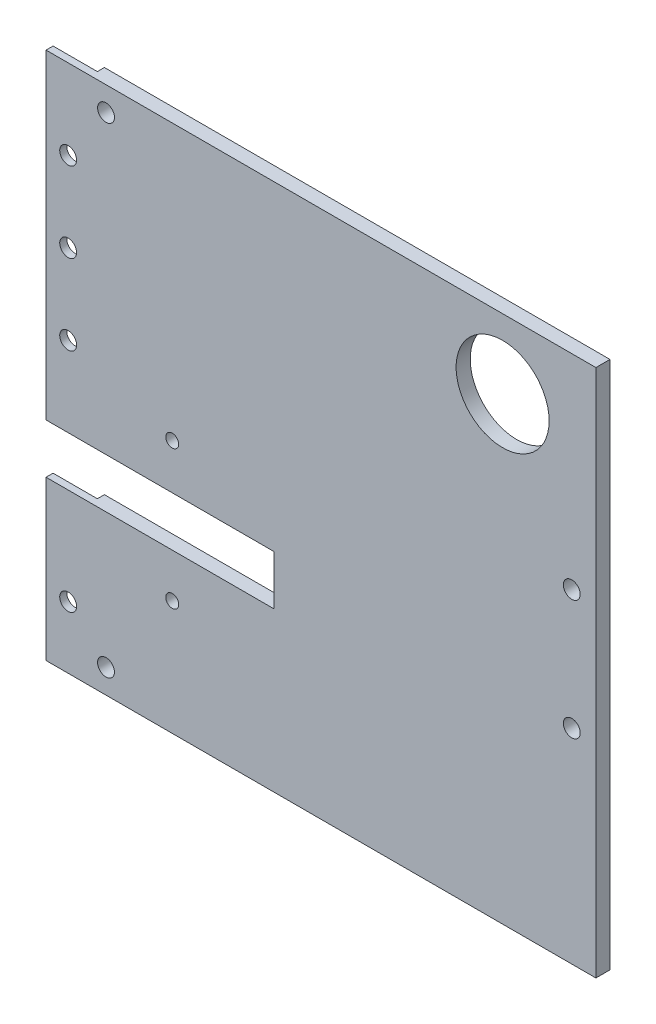
SolidWorks part; units mm, degrees
ref_plane "Front Plane" through (0, 0, 0) normal (0, 0, 1) x (1, 0, 0)
ref_plane "Top Plane" through (0, 0, 0) normal (0, 1, 0) x (1, 0, 0)
ref_plane "Right Plane" through (0, 0, 0) normal (1, 0, 0) x (0, 0, -1)
sketch "Sketch2" plane through (0, -1.0615, 0) normal (0, 0, 1) x (1, 0, 0)
  line L1 (-61.3763, 33.8617) -> (62.7937, 33.8617)
  line L2 (-61.3763, 33.8617) -> (-61.3763, -85.5183)
  line L3 (-61.3763, -85.5183) -> (62.7937, -85.5183)
  line L4 (62.7937, 33.8617) -> (62.7937, -85.5183)
  dimension "D1" = 124.17
  dimension "D2" = 119.38
extrude "Boss-Extrude1" add sketch "Sketch2" along normal blind 3.18
sketch "Sketch3" plane through (0, 0, 0) normal (0, 0, 1) x (1, 0, 0)
  line L0 (-61.3763, 32.8002) -> (-61.3763, -86.5798) construction
  line L1 (-61.3763, -39.5328) -> (-9.8763, -39.5328)
  line L2 (-61.3763, -39.5328) -> (-61.3763, -50.7328)
  line L3 (-61.3763, -50.7328) -> (-9.8763, -50.7328)
  line L4 (-9.8763, -39.5328) -> (-9.8763, -50.7328)
  line L8 (62.7937, 32.8002) -> (-61.3763, 32.8002) construction
  line L9 (62.7937, -86.5798) -> (62.7937, 32.8002) construction
  line L10 (-61.3763, -86.5798) -> (62.7937, -86.5798) construction
  circle A0 centre (-32.8763, -60.6688) radius 1.46
  circle A1 centre (-32.8763, -29.3188) radius 1.46
  circle A2 centre (-47.8263, 27.3482) radius 1.905
  circle A3 centre (41.7297, 17.0902) radius 10.5
  circle A4 centre (-47.8263, -81.1278) radius 1.905
  circle A5 centre (57.3437, -13.3398) radius 1.905
  circle A6 centre (57.3437, -40.4398) radius 1.905
  dimension "D5" = 5.452
  dimension "D1" = 15.71
  dimension "D3" = 21
  dimension "D2" = 21.064
  dimension "D4" = 5.452
  dimension "D6" = 35.847
  dimension "D7" = 25.911
  dimension "D8" = 11.2
  dimension "D9" = 27.1
  dimension "D10" = 46.14
  dimension "D11" = 13.55
  dimension "D12" = 10.214
  dimension "D13" = 28.5
  dimension "D14" = 28.5
  dimension "D15" = 51.5
  dimension "D16" = 9.936
  dimension "D17" = 13.55
extrude "Cut-Extrude1" cut sketch "Sketch3" along normal blind 23.18
sketch "Sketch5" plane through (-61.3763, 0, 0) normal (-1, 0, 0) x (0, 0, 1)
  line L1 (0, 32.8002) -> (1.59, 32.8002)
  line L2 (0, 32.8002) -> (0, -87.1998)
  line L3 (0, -87.1998) -> (1.59, -87.1998)
  line L4 (1.59, 32.8002) -> (1.59, -87.1998)
  dimension "D1" = 1.59
  dimension "D2" = 120
extrude "Cut-Extrude2" cut sketch "Sketch5" against normal blind 10
sketch "Sketch6" plane through (0, 0, 1.59) normal (0, 0, -1) x (-1, 0, 0)
  line L0 (61.3763, -39.5328) -> (61.3763, 32.8002) construction
  line L1 (61.3763, -86.5798) -> (61.3763, -50.7328) construction
  line L2 (51.3763, 32.8002) -> (61.3763, 32.8002) construction
  line L3 (51.3763, -39.5328) -> (61.3763, -39.5328) construction
  circle A0 centre (56.3763, 14.7202) radius 1.905
  circle A1 centre (56.3763, -3.3698) radius 1.905
  circle A2 centre (56.3763, -21.4528) radius 1.905
  circle A3 centre (56.3763, -72.5798) radius 1.905
  dimension "D1" = 5
  dimension "D2" = 5
  dimension "D3" = 5
  dimension "D4" = 5
  dimension "D6" = 18.08
  dimension "D7" = 36.17
  dimension "D8" = 18.08
extrude "Cut-Extrude3" cut sketch "Sketch6" against normal blind 10
